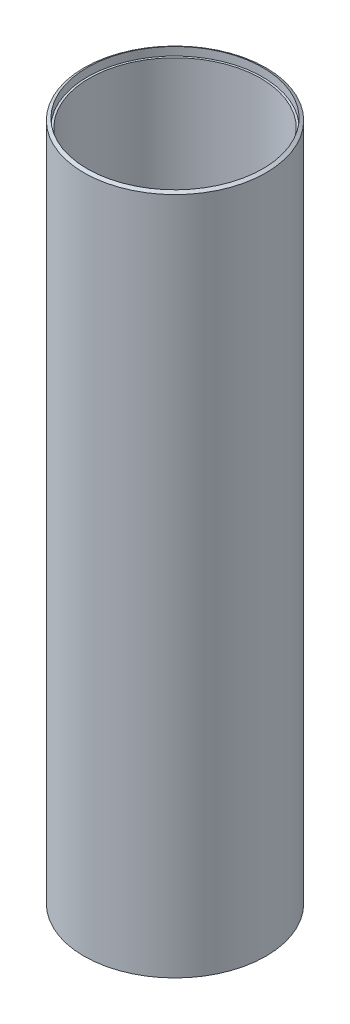
SolidWorks part; units mm, degrees
material "6061-T6 (SS)"
ref_plane "Front Plane" through (0, 0, 0) normal (0, 0, 1) x (1, 0, 0)
ref_plane "Top Plane" through (0, 0, 0) normal (0, 1, 0) x (1, 0, 0)
ref_plane "Right Plane" through (0, 0, 0) normal (1, 0, 0) x (0, 0, -1)
ref_axis "Axis1" through (0, 819.187, 0) along (0, -1, 0)
sketch "Sketch2" plane through (0, 0, 0) normal (0, 0, 1) x (1, 0, 0)
  line L0 (-69.85, 1.4298) -> (-69.85, 522.1298)
  line L1 (-67.3735, 0) -> (-69.85, 1.4298)
  line L2 (-65.786, 6.35) -> (-65.786, 517.2096)
  line L3 (-67.3735, 0) -> (-67.3735, 6.35)
  line L4 (-69.85, 261.7798) -> (-65.786, 261.7798) construction
  line L5 (0, 819.187) -> (0, -55) construction
  line L6 (-67.3735, 523.5596) -> (-69.85, 522.1298)
  line L7 (-67.3735, 517.2096) -> (-65.786, 517.2096)
  line L8 (-67.3735, 523.5596) -> (-67.3735, 517.2096)
  line L9 (-67.3735, 6.35) -> (-65.786, 6.35)
  line L13 (55, 0) -> (-55, 0) construction
  point P1 (-69.85, 261.7798)
  point P17 (-65.786, 261.7798)
  dimension "D2" = 4.064
  dimension "D3" = 260.35
  dimension "D4" = 69.85
  dimension "D6" = 60
  dimension "D10" = 1.5875
  dimension "D11" = 6.35
revolve "Revolve1" add sketch "Sketch2" angle 360 about axis through (0, 819.187, 0) along (0, -1, 0)
